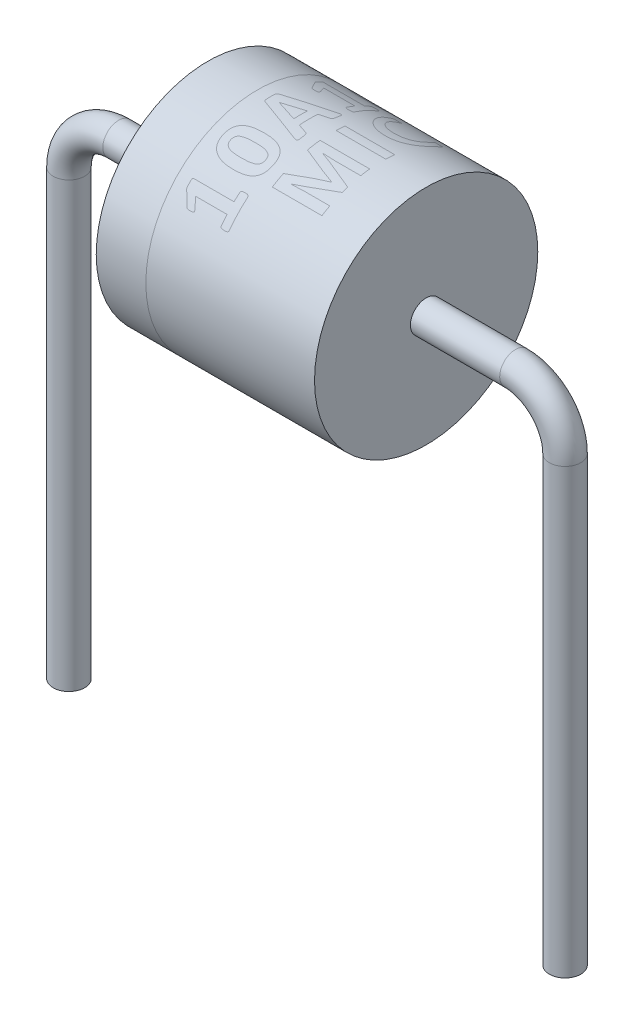
SolidWorks part; units mm, degrees
other "Wire"
other "Cathode Silver Band"
other "Diode"
ref_plane "Front Plane" through (0, 0, 0) normal (0, 0, 1) x (1, 0, 0)
ref_plane "Top Plane" through (0, 0, 0) normal (0, 1, 0) x (1, 0, 0)
ref_plane "Right Plane" through (0, 0, 0) normal (1, 0, 0) x (0, 0, -1)
sketch "Sketch1" plane through (0, 0, 0) normal (1, 0, 0) x (0, 0, -1)
  circle A0 centre (0, 0) radius 4.5
  circle A1 centre (0, 0) radius 0.635
  dimension "D1" = 9
  dimension "D2" = 1.27
extrude "Boss-Extrude1" add sketch "Sketch1" along normal mid plane 8.8
sketch "Sketch2" plane through (-4.4, 0, 0) normal (-1, 0, 0) x (0, 0, 1)
  circle A1 centre (0, 0) radius 4.5 construction
  circle A2 centre (0, 0) radius 4.49
  circle A3 centre (0, 0) radius 4.49
  circle A4 centre (0, 0) radius 4.5
  dimension "D1" = 0.01
extrude "Cut-Extrude1" cut sketch "Sketch2" against normal blind 2
sketch "Sketch3" plane through (-2.4, 0, 0) normal (-1, 0, 0) x (0, 0, 1)
  circle A0 centre (0, 0) radius 4.49 construction
  circle A1 centre (0, 0) radius 4.49
  circle A2 centre (0, 0) radius 4.5 construction
  circle A3 centre (0, 0) radius 4.5
extrude "Boss-Extrude2" add sketch "Sketch3" along normal up to surface (2 mm away) separate body up to face at (-4.4, 0, -0.635)
ref_plane "Plane1" through (0, 5, 0) normal (0, 1, 0) x (1, 0, 0)
sketch "Sketch4" plane through (0, 5, 0) normal (0, 1, 0) x (1, 0, 0)
  line L0 (0.1, 7.5) -> (0.1, -7.5) construction
  line L1 (0.1, 0) -> (-4.4, 0) construction
  line L2 (-4.4, 4.5) -> (-4.4, -4.5) construction
  line L4 (0.1, 0) -> (2.6, 0) construction
  line L5 (2.6, 7.5) -> (2.6, -7.5) construction
  text T0 "10A10" font "Calibri" height 2
  text T1 "MIC" font "Corbel" height 2
  dimension "D1" = 4.5
  dimension "D2" = 15
  dimension "D3" = 2.5
wrap "Wrap1" sketch "Sketch4" wrap type scribe source sketch "Sketch4" face at (4.4, 0, -4.5)
sketch "Sketch5" plane through (0, 0, 0) normal (0, 0, 1) x (1, 0, 0)
  line L0 (0, 0) -> (-8, 0)
  line L1 (-10, -2) -> (-10, -19.8584)
  line L2 (0, 0) -> (8, 0)
  line L3 (10, -2) -> (10, -19.8584)
  arc A0 (-8, 0) -> (-10, -2) centre (-8, -2) ccw
  arc A1 (8, 0) -> (10, -2) centre (8, -2) cw
  dimension "D2" = 2
  dimension "D3" = 58
  dimension "D1" = 20
sketch "Sketch6" plane through (0, 0, 0) normal (1, 0, 0) x (0, 0, -1)
  circle A0 centre (0, 0) radius 0.635
  dimension "D1" = 1.27
sweep "Sweep1" add profiles "Sketch6" path "Sketch5"
